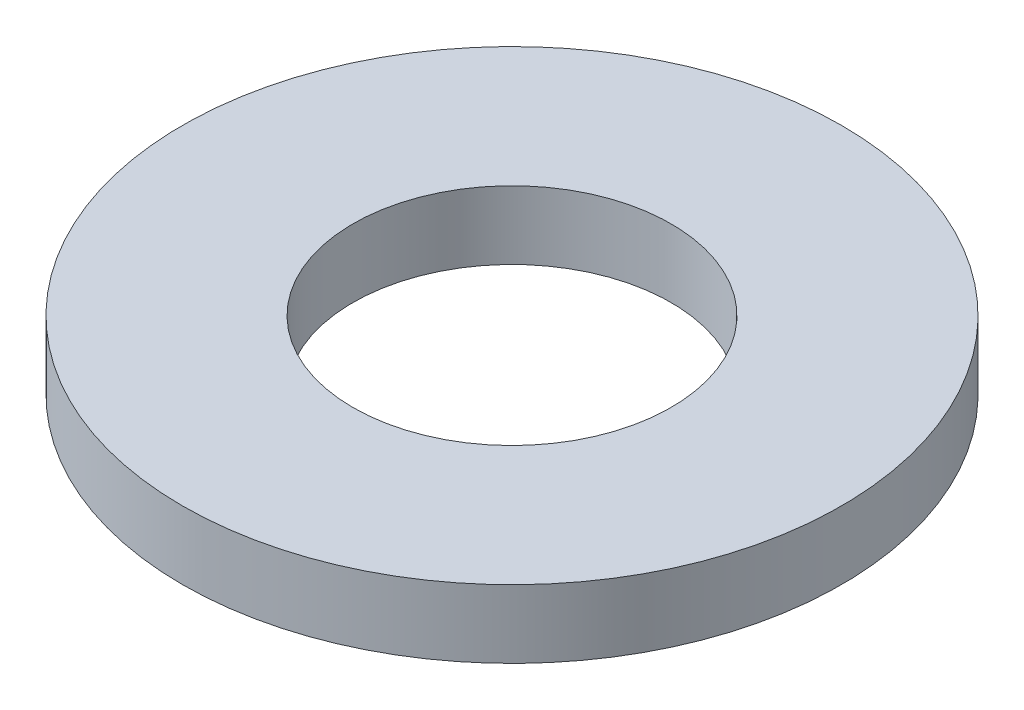
SolidWorks part; units mm, degrees
ref_plane "Front Plane" through (0, 0, 0) normal (0, 0, 1) x (1, 0, 0)
ref_plane "Top Plane" through (0, 0, 0) normal (0, 1, 0) x (1, 0, 0)
ref_plane "Right Plane" through (0, 0, 0) normal (1, 0, 0) x (0, 0, -1)
sketch "Sketch1" plane through (0, 0, 0) normal (0, 1, 0) x (1, 0, 0)
  circle A0 centre (0, 0) radius 72.5
  dimension "FLANGE_OD" = 145
extrude "Boss-Extrude1" add sketch "Sketch1" along normal blind 15
sketch "Sketch2" plane through (0, 0, 0) normal (0, 1, 0) x (1, 0, 0)
  circle A0 centre (0, 0) radius 35
  dimension "BORE_D" = 70
extrude "Cut-Extrude1" cut sketch "Sketch2" along normal through all
sketch "Sketch3" plane through (0, 15, 0) normal (0, 1, 0) x (1, 0, 0)
  circle A0 centre (0, 0) radius 21.0925 construction
  circle A1 centre (-21.0925, 0) radius 4.4543
  dimension "BOLT_D" = 8.9086
  dimension "BOLT_PCD" = 42.1851
extrude "Cut-Extrude2" cut sketch "Sketch3" against normal blind 11.9276 rebuild error yes
pattern_circular "CirPattern1" count 5 over 360 rebuild error yes
